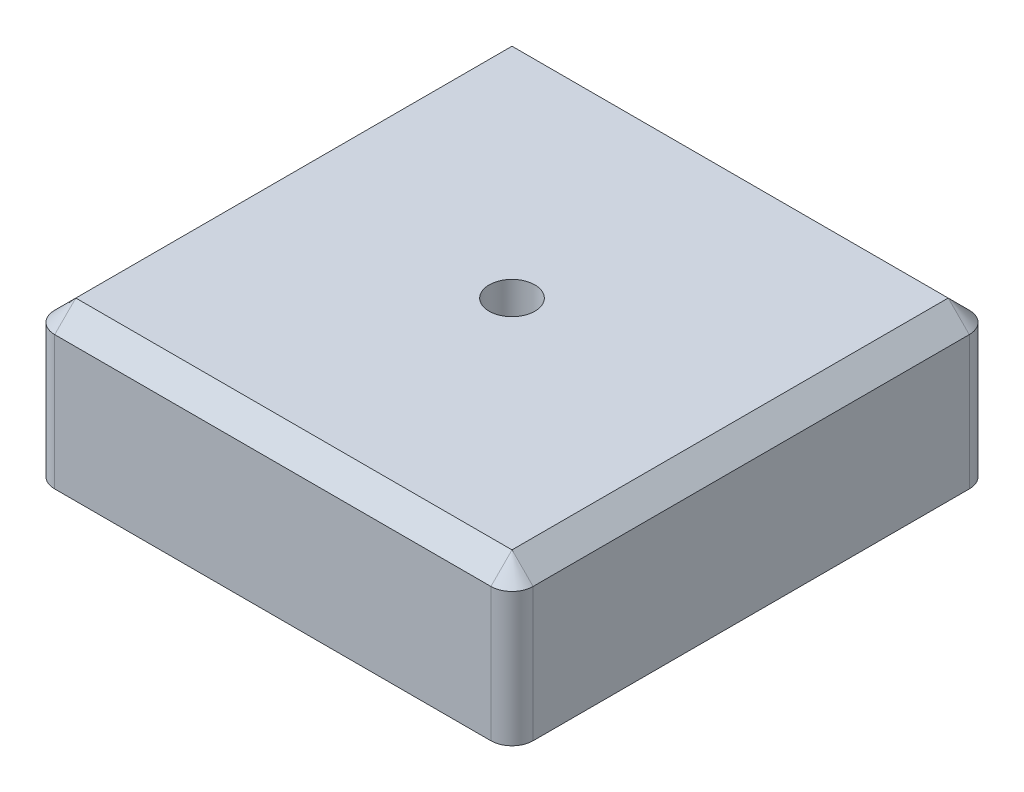
SolidWorks part; units mm, degrees
ref_plane "Front Plane" through (0, 0, 0) normal (0, 0, 1) x (1, 0, 0)
ref_plane "Top Plane" through (0, 0, 0) normal (0, 1, 0) x (1, 0, 0)
ref_plane "Right Plane" through (0, 0, 0) normal (1, 0, 0) x (0, 0, -1)
sketch "Sketch1" plane through (0, 0, 0) normal (0, 1, 0) x (1, 0, 0)
  line L1 (-34, 34) -> (34, 34)
  line L2 (-34, 34) -> (-34, -34)
  line L3 (-34, -34) -> (34, -34)
  line L4 (34, 34) -> (34, -34)
  line L5 (-34, 34) -> (34, -34) construction
  line L6 (-34, -34) -> (34, 34) construction
  point P0 (0, 0)
  dimension "D1" = 68
extrude "Boss-Extrude1" add sketch "Sketch1" along normal blind 10
sketch "Sketch4" plane through (0, 0, 0) normal (0, -1, 0) x (1, 0, 0)
  line L1 (-15, 15) -> (15, 15)
  line L2 (-15, 15) -> (-15, -15)
  line L3 (-15, -15) -> (15, -15)
  line L4 (15, 15) -> (15, -15)
  line L5 (-15, 15) -> (15, -15) construction
  line L6 (-15, -15) -> (15, 15) construction
  line L10 (34, -34) -> (34, 34)
  line L11 (34, 34) -> (-34, 34)
  line L12 (-34, 34) -> (-34, -34)
  line L13 (-34, -34) -> (34, -34)
  line L14 (34, -34) -> (34, 34)
  line L15 (34, 34) -> (-34, 34)
  line L16 (-34, 34) -> (-34, -34)
  line L17 (-34, -34) -> (34, -34)
  point P0 (0, 0)
  dimension "D1" = 30
  dimension "D2" = 0
extrude "Boss-Extrude3" add sketch "Sketch4" along normal blind 12
fillet "Fillet2" radius 3 4 edges at (34, -1, 34) (-34, -1, 34) (34, -1, -34) (-34, -1, -34)
fillet "Fillet3" radius 3 4 edges at (-15, -6, 15) (-15, -6, -15) (15, -6, -15) (15, -6, 15)
sketch "Sketch5" plane through (0, 0, 0) normal (0, -1, 0) x (1, 0, 0)
  circle A0 centre (0, 0) radius 3.25
  dimension "D1" = 6.5
extrude "Cut-Extrude2" cut sketch "Sketch5" against normal blind 20
chamfer "Chamfer1" distance 3 angle 45 8 edges at (33.1213, 10, -33.1213) (34, 10, 0) (33.1213, 10, 33.1213) (0, 10, -34) (-33.1213, 10, -33.1213) (-34, 10, 0) (-33.1213, 10, 33.1213) (0, 10, 34)
chamfer "Chamfer2" distance 3 angle 45 8 edges at (-14.1213, 0, -14.1213) (0, 0, -15) (-15, 0, 0) (14.1213, 0, -14.1213) (-14.1213, 0, 14.1213) (15, 0, 0) (0, 0, 15) (14.1213, 0, 14.1213)
